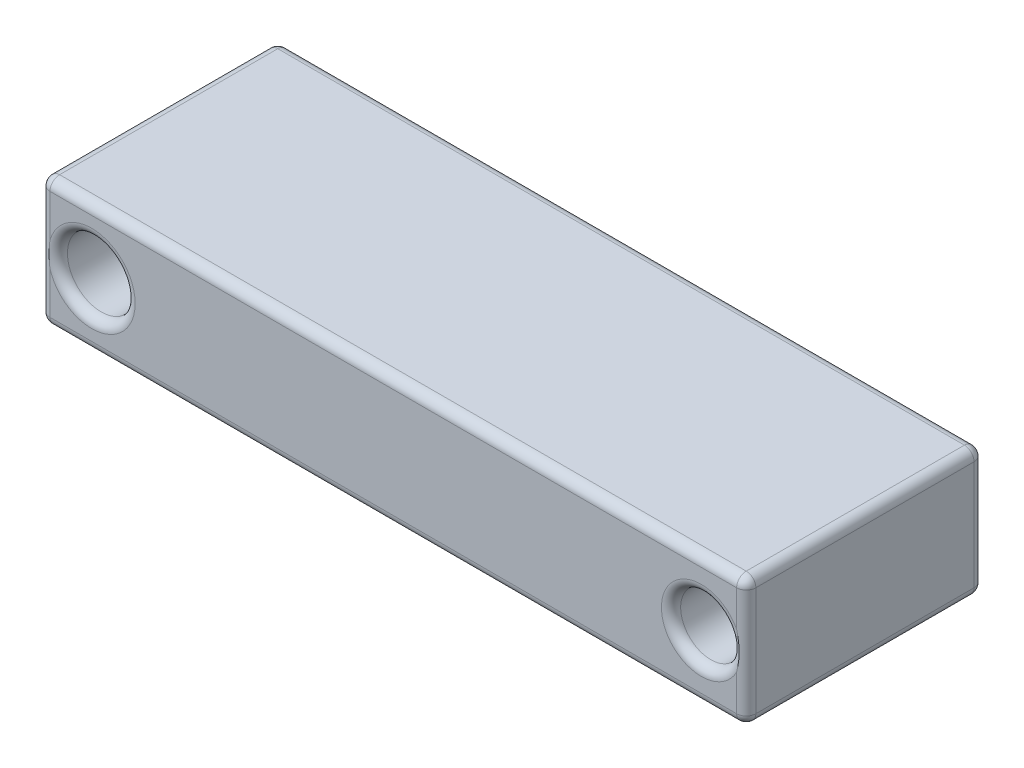
SolidWorks part; units mm, degrees
ref_plane "Front Plane" through (0, 0, 0) normal (0, 0, 1) x (1, 0, 0)
ref_plane "Top Plane" through (0, 0, 0) normal (0, 1, 0) x (1, 0, 0)
ref_plane "Right Plane" through (0, 0, 0) normal (1, 0, 0) x (0, 0, -1)
sketch "Sketch1" plane through (0, 0, 0) normal (0, 0, 1) x (1, 0, 0)
  line L1 (-95.3819, 55.5062) -> (14.6181, 55.5062)
  line L2 (-95.3819, 55.5062) -> (-95.3819, 35.5062)
  line L3 (-95.3819, 35.5062) -> (14.6181, 35.5062)
  line L4 (14.6181, 55.5062) -> (14.6181, 35.5062)
  dimension "D1" = 110
  dimension "D2" = 20
extrude "Extrude1" add sketch "Sketch1" along normal blind 37
sketch "Sketch2" plane through (0, 0, 37) normal (0, 0, 1) x (1, 0, 0)
  line L0 (14.6181, 35.5062) -> (14.6181, 55.5062) construction
  line L1 (-95.3819, 35.5062) -> (14.6181, 35.5062) construction
  circle A0 centre (-87.3819, 45.5062) radius 5.275
  circle A1 centre (7.6181, 45.5062) radius 4.714
  point P4 (14.6181, 45.5062)
  dimension "D1" = 95
  dimension "D2" = 7
  dimension "D3" = 10
  dimension "D4" = 10
extrude "Extrude2" cut sketch "Sketch2" against normal blind 110
fillet "Fillet1" radius 1.5 16 edges at (-95.3819, 35.5062, 18.5) (-40.3819, 35.5062, 0) (-95.3819, 45.5062, 0) (-82.1069, 45.5062, 0) (12.3321, 45.5062, 0) (14.6181, 35.5062, 18.5) (14.6181, 45.5062, 0) (14.6181, 55.5062, 18.5) (-95.3819, 55.5062, 18.5) (-40.3819, 55.5062, 0) (-40.3819, 55.5062, 37) (14.6181, 45.5062, 37) (-40.3819, 35.5062, 37) (-95.3819, 45.5062, 37) (-82.1069, 45.5062, 37) (12.3321, 45.5062, 37)
